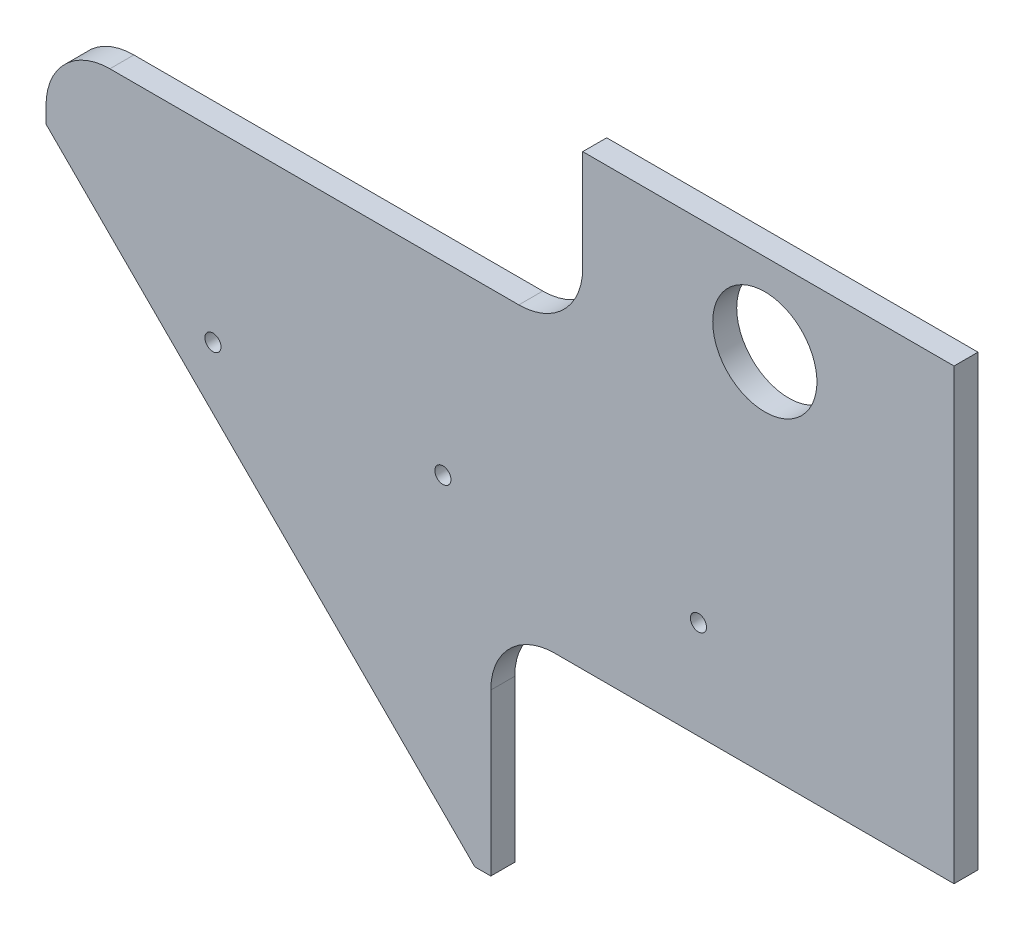
SolidWorks part; units mm, degrees
ref_plane "Front Plane" through (0, 0, 0) normal (0, 0, 1) x (1, 0, 0)
ref_plane "Top Plane" through (0, 0, 0) normal (0, 1, 0) x (1, 0, 0)
ref_plane "Right Plane" through (0, 0, 0) normal (1, 0, 0) x (0, 0, -1)
sketch "Sketch1" plane through (0, 0, 0) normal (0, 0, 1) x (1, 0, 0)
  line L0 (-138.2594, 48.9915) -> (32.2106, -121.4785)
  line L1 (32.2106, -121.4785) -> (222.7106, -121.4785)
  line L2 (-138.2594, 146.2068) -> (-138.2594, 48.9915)
  line L3 (-138.2594, 146.2068) -> (222.7106, 146.2068)
  line L4 (222.7106, -121.4785) -> (222.7106, 146.2068)
  circle A0 centre (147.4906, 113.4715) radius 20.701
  circle A2 centre (147.4906, 113.4715) radius 69.85 construction
  circle A3 centre (147.4906, 113.4715) radius 285.75 construction
  point P0 (0, 0)
  point P2 (147.4906, 113.4715)
  dimension "D4" = 234.95
  dimension "D1" = 45
  dimension "D2" = 267.6854
  dimension "D5" = 247.65
extrude "Boss-Extrude1" add sketch "Sketch1" along normal blind 9.525
sketch "Sketch2" plane through (0, 0, 9.525) normal (0, 0, 1) x (1, 0, 0)
  line L0 (32.2106, -121.4785) -> (222.7106, -121.4785) construction
  line L1 (222.7106, -121.4785) -> (38.5606, -121.4785)
  line L2 (222.7106, -121.4785) -> (222.7106, -32.0424)
  line L3 (222.7106, -32.0424) -> (38.5606, -32.0424)
  line L4 (38.5606, -121.4785) -> (38.5606, -32.0424)
extrude "Cut-Extrude1" cut sketch "Sketch2" against normal through all contours L3 L4 L1 L2
fillet "Fillet1" radius 25.4 1 edges at (38.5606, -32.0424, 4.7625)
sketch "Sketch4" plane through (0, 0, 9.525) normal (0, 0, 1) x (1, 0, 0)
  line L1 (-138.2594, 146.2068) -> (-138.2594, 48.9915) construction
  line L3 (-138.2594, 146.2068) -> (75.1006, 146.2068)
  line L4 (-138.2594, 146.2068) -> (-138.2594, 80.7415)
  line L5 (-138.2594, 80.7415) -> (75.1006, 80.7415)
  line L6 (75.1006, 146.2068) -> (75.1006, 80.7415)
extrude "Cut-Extrude2" cut sketch "Sketch4" against normal through all contours L5 L6 L3 L4
fillet "Fillet2" radius 25.4 2 edges at (-138.2594, 80.7415, 4.7625) (75.1006, 80.7415, 4.7625)
hole_wizard "Ø6.4 (6.4) Diameter Hole2" positions "Sketch15" profile "Sketch14" hole size "Ø6.4" standard "Lanco STD" end condition through all
sketch "Sketch15" plane through (0, 0, 0) normal (0, 0, -1) x (-1, 0, 0)
  point P3 (-121.1106, 7.0429)
  point P6 (-19.5106, 7.0429)
  point P9 (71.8957, 7.0429)
sketch "Sketch14" plane through (121.1106, 7.0429, 0) normal (1, 0, 0) x (0, 1, 0)
  line L0 (0, 0) -> (0, 9.525)
  line L1 (0, 9.525) -> (3.2, 9.525)
  line L2 (3.2, 9.525) -> (3.2, 0)
  line L5 (3.2, 0) -> (0, 0)
  line L11 (0, -6.35) -> (0, 107.95) construction
  dimension "Thru Hole Dia." = 6.4
  dimension "Thru Hole Depth" = 9.525
